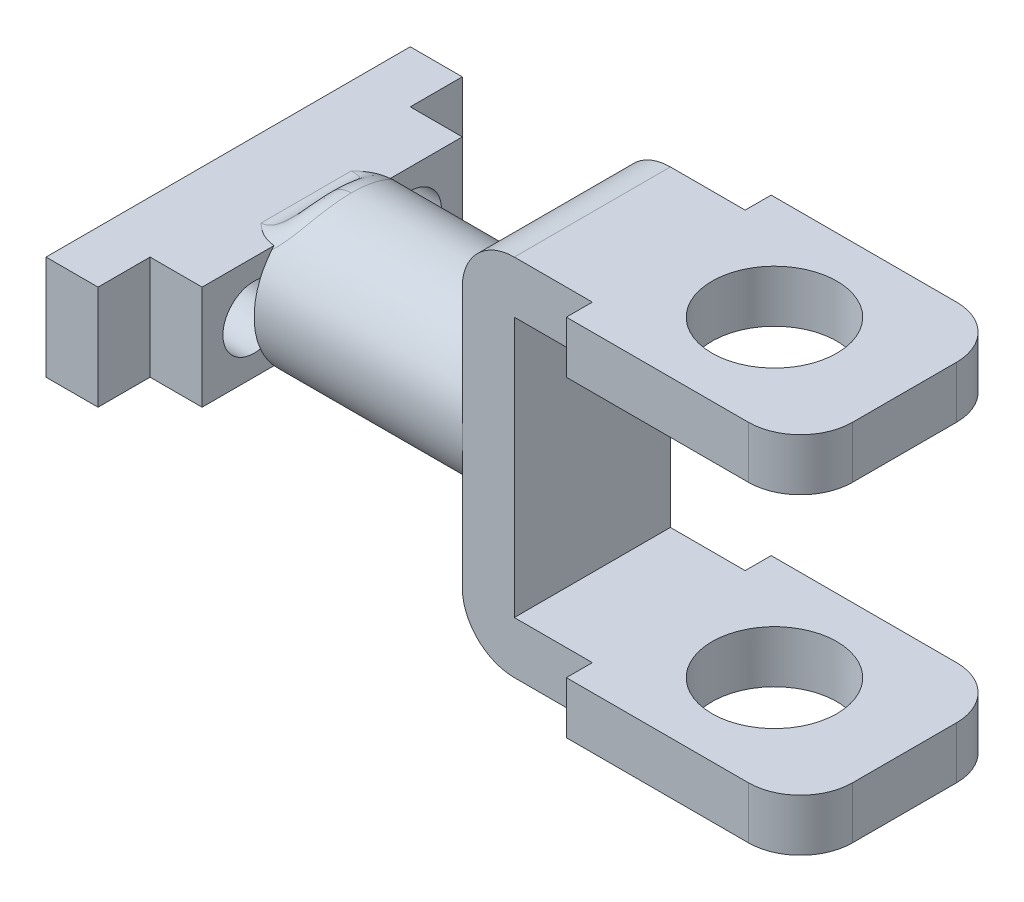
SolidWorks part; units mm, degrees
ref_plane "Front Plane" through (0, 0, 0) normal (0, 0, 1) x (1, 0, 0)
ref_plane "Top Plane" through (0, 0, 0) normal (0, 1, 0) x (1, 0, 0)
ref_plane "Right Plane" through (0, 0, 0) normal (1, 0, 0) x (0, 0, -1)
sketch "Sketch1" plane through (0, 0, 0) normal (0, 1, 0) x (1, 0, 0)
  line L2 (-4, -2.5) -> (-4, 2.5)
  line L3 (-4, 2.5) -> (4, 2.5)
  line L4 (4, 2.5) -> (4, -2.5)
  line L22 (0, 2.5) -> (0, -2.5) construction
  line L23 (-4, -2.5) -> (4, -2.5)
  point P1 (0, 0)
  point P6 (0, 0)
  dimension "D1" = 5
  dimension "D2" = 8
extrude "Boss-Extrude1" add sketch "Sketch1" along normal mid plane 5
sketch "Sketch2" plane through (0, 0, 0) normal (0, 1, 0) x (1, 0, 0)
  line L0 (-1.5, -2.5) -> (1.5, -2.5)
  line L1 (-1.5, -2.5) -> (-1.5, -5.5)
  line L2 (-1.5, -5.5) -> (1.5, -5.5)
  line L3 (1.5, -2.5) -> (1.5, -5.5)
  line L4 (-4, -2.5) -> (4, -2.5) construction
  dimension "D1" = 3
  dimension "D2" = 3
extrude "Boss-Extrude2" add sketch "Sketch2" along normal mid plane 3
sketch "Sketch3" plane through (0, 0, 5.5) normal (0, 0, 1) x (1, 0, 0)
  line L4 (-1.5, -1.5) -> (1.5, -1.5)
  line L5 (1.5, -1.5) -> (1.5, 1.5)
  line L6 (1.5, 1.5) -> (-1.5, 1.5)
  line L7 (-1.5, 1.5) -> (-1.5, -1.5)
  line L8 (-1.5, -1.5) -> (1.5, -1.5)
  line L9 (1.5, -1.5) -> (1.5, 1.5)
  line L10 (1.5, 1.5) -> (-1.5, 1.5)
  line L11 (-1.5, 1.5) -> (-1.5, -1.5)
  circle A0 centre (0, 0) radius 1.5
  line M6 (-1.5, -1.5) -> (1.5, -1.5)
  line M7 (1.5, -1.5) -> (1.5, 1.5)
  line M8 (1.5, 1.5) -> (-1.5, 1.5)
  line M9 (-1.5, 1.5) -> (-1.5, -1.5)
  dimension "D1" = 0
extrude "Cut-Extrude2" cut sketch "Sketch3" against normal up to surface (3 mm away) contours A0 L10 M9 | A0 L9 M8 | A0 L8 M7 | A0 L11 M6 region at (-1.1649, -1.1649, 5.5) region at (1.1649, -1.1649, 5.5) region at (-1.1649, 1.1649, 5.5) region at (1.1649, 1.1649, 5.5) up to face at (0, 0, 2.5)
sketch "Sketch5" plane through (0, 2.5, 0) normal (0, 1, 0) x (1, 0, 0)
  circle A0 centre (0, 0) radius 1.2
extrude "Cut-Extrude3" cut sketch "Sketch5" against normal through all
sketch "Sketch6" plane through (0, 0, 2.5) normal (0, 0, 1) x (1, 0, 0)
  line L0 (-4, -2.5) -> (4, -2.5) construction
  line L1 (-4, 2.5) -> (-4, -2.5) construction
  line L2 (-4, 2.5) -> (4, 2.5) construction
  line L3 (-4, -2.5) -> (4, -2.5)
  line L4 (-4, 2.5) -> (-4, -2.5)
  line L5 (-4, 2.5) -> (4, 2.5)
  line L6 (-5, -3.5) -> (4, -3.5)
  line L7 (-5, 3.5) -> (-5, -3.5)
  line L8 (-5, 3.5) -> (4, 3.5)
  line L9 (4, 3.5) -> (4, 2.5)
  line L10 (4, -2.5) -> (4, -3.5)
  dimension "D1" = 1
extrude "Boss-Extrude3" add sketch "Sketch6" along normal mid plane 4
sketch "Sketch7" plane through (0, 0, 2.5) normal (0, 0, 1) x (1, 0, 0)
  line L4 (-4, -2.5) -> (4, -2.5)
  line L5 (4, -2.5) -> (4, 2.5)
  line L6 (4, 2.5) -> (-4, 2.5)
  line L7 (-4, 2.5) -> (-4, -2.5)
  line L8 (-4, -2.5) -> (4, -2.5)
  line L9 (4, -2.5) -> (4, 2.5)
  line L10 (4, 2.5) -> (-4, 2.5)
  line L11 (-4, 2.5) -> (-4, -2.5)
  dimension "D1" = 0
extrude "Cut-Extrude5" cut sketch "Sketch7" against normal through all and the other way through all
sketch "Sketch8" plane through (-5, 0, 0) normal (-1, 0, 0) x (0, 0, 1)
  line L0 (0.5, 0) -> (4.5, 0) construction
  line L1 (0.5, 3.5) -> (0.5, -3.5) construction
  line L2 (4.5, 3.5) -> (4.5, -3.5) construction
  circle A0 centre (2.5, 0) radius 1.5
extrude "Boss-Extrude5" add sketch "Sketch8" along normal blind 5
sketch "Sketch9" plane through (0, 3.5, 0) normal (0, 1, 0) x (1, 0, 0)
  line L0 (-5, -2.5) -> (4, -2.5) construction
  line L1 (-5, -1) -> (-5, -4) construction
  line L2 (4, -4.5) -> (4, -0.5) construction
  circle A0 centre (-0.5, -2.5) radius 1.2
extrude "Cut-Extrude6" cut sketch "Sketch9" against normal through all
fillet "Fillet1" radius 1 6 edges at (-5, -3.5, 2.5) (-5, 3.5, 2.5) (4, -3, 0.5) (4, -3, 4.5) (4, 3, 4.5) (4, 3, 0.5)
sketch "Sketch10" plane through (0, 3.5, 0) normal (0, 1, 0) x (1, 0, 0)
  line L0 (-5, -1) -> (-10, -1) construction
  line L1 (-5, -0.5) -> (-2.5631, -0.5)
  line L2 (-5, -0.5) -> (-5, -1)
  line L3 (-5, -1) -> (-2.5631, -1)
  line L4 (-2.5631, -0.5) -> (-2.5631, -1)
  line L5 (-5, -4.5) -> (-2.5, -4.5)
  line L6 (-5, -4.5) -> (-5, -4)
  line L7 (-5, -4) -> (-2.5, -4)
  line L8 (-2.5, -4.5) -> (-2.5, -4)
  line L9 (-10, -4) -> (-5, -4) construction
  dimension "D1" = 2.5
extrude "Cut-Extrude7" cut sketch "Sketch10" against normal through all
sketch "Sketch11" plane through (0, 3.5, 0) normal (0, 1, 0) x (1, 0, 0)
  line L0 (3, -0.5) -> (-2.5631, -0.5) construction
  line L1 (2, -0.5) -> (4, -0.5)
  line L2 (2, -0.5) -> (2, -4.5)
  line L3 (2, -4.5) -> (4, -4.5)
  line L4 (4, -0.5) -> (4, -4.5)
  line L5 (3, -4.5) -> (-2.5, -4.5) construction
  line L6 (4, -3.5) -> (4, -1.5) construction
  dimension "D1" = 2
extrude "Cut-Extrude8" cut sketch "Sketch11" against normal through all
fillet "Fillet3" radius 1 4 edges at (2, -3, 4.5) (2, -3, 0.5) (2, 3, 0.5) (2, 3, 4.5)
sketch "Sketch12" plane through (-10, 0, 0) normal (-1, 0, 0) x (0, 0, 1)
  line L0 (-1, 1) -> (6, 1)
  line L1 (-1, 1) -> (-1, -1)
  line L2 (-1, -1) -> (6, -1)
  line L3 (6, 1) -> (6, -1)
  line L4 (2.5, 1) -> (2.5, -1) construction
  line L5 (2.5, 1.5) -> (2.5, -1.5) construction
  circle A0 centre (4, 0) radius 0.6
  circle A1 centre (1, 0) radius 0.6
  arc A2 (4, 0) -> (1, 0) centre (2.5, 0) ccw construction
  arc A3 (1, 0) -> (4, 0) centre (2.5, 0) ccw construction
  point P18 (2.5, 0)
  point P19 (2.5, 0)
  dimension "D1" = 2
  dimension "D2" = 7
  dimension "D3" = 2
  dimension "D4" = 1
  dimension "D5" = 2
  dimension "D6" = 1
  dimension "D7" = 1
  dimension "D8" = 2
  dimension "D9" = 7
extrude "Boss-Extrude6" add sketch "Sketch12" along normal blind 1
sketch "Sketch13" plane through (-10, 0, 0) normal (1, 0, 0) x (0, 0, -1)
  line L0 (-2.5, 1) -> (-2.5, -1) construction
  line L1 (-6, 1) -> (1, 1) construction
  line L2 (1, -1) -> (-6, -1) construction
  line L4 (0, 1) -> (-5, 1)
  line L5 (0, 1) -> (0, -1)
  line L6 (0, -1) -> (-5, -1)
  line L7 (-5, 1) -> (-5, -1)
  line L8 (0, 1) -> (-5, -1) construction
  line L9 (0, -1) -> (-5, 1) construction
  point P6 (-2.5, 0)
  dimension "D1" = 5
extrude "Boss-Extrude7" add sketch "Sketch13" along normal blind 1
sketch "Sketch14" plane through (-10, 0, 0) normal (-1, 0, 0) x (0, 0, 1)
  line L1 (1.382, 1) -> (3.618, 1)
  line L2 (1.382, 1) -> (3.618, 1)
  line L3 (3.618, -1) -> (1.382, -1)
  line L4 (3.618, -1) -> (1.382, -1)
  arc A1 (3.618, 1) -> (1.382, 1) centre (2.5, 0) ccw
  arc A2 (3.618, 1) -> (1.382, 1) centre (2.5, 0) ccw
  arc A3 (1.382, -1) -> (3.618, -1) centre (2.5, 0) ccw
  arc A4 (1.382, -1) -> (3.618, -1) centre (2.5, 0) ccw
  dimension "D1" = 0
  dimension "D2" = 0
extrude "Cut-Extrude9" cut sketch "Sketch14" against normal up to surface (1 mm away) up to face at (-9, 0, 4.4045)
fillet "Fillet5" radius 0.5 2 edges at (-9, -1, 2.5) (-9, 1, 2.5)
sketch "Sketch15" plane through (-11, 0, 0) normal (-1, 0, 0) x (0, 0, 1)
  circle A0 centre (4, 0) radius 0.6 construction
  circle A1 centre (1, 0) radius 0.6 construction
  circle A2 centre (4, 0) radius 0.6
  circle A3 centre (1, 0) radius 0.6
extrude "Cut-Extrude10" cut sketch "Sketch15" against normal up to surface (2 mm away) up to face at (-9, 0, 4.4045)
fillet "Fillet6" radius 0.5 4 edges at (-9.1332, -1.1602, 1.5492) (-9.1608, 1.1326, 1.5166) (-9.1608, -1.1326, 3.4834) (-9.1332, 1.1602, 3.4508)
